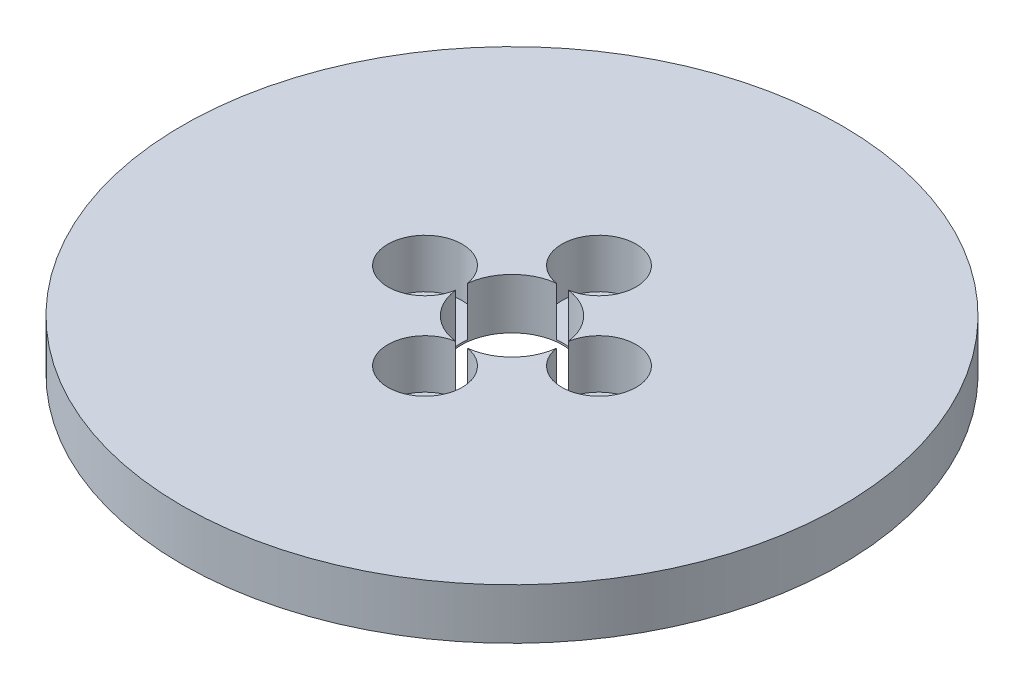
SolidWorks part; units mm, degrees
ref_plane "Front Plane" through (0, 0, 0) normal (0, 0, 1) x (1, 0, 0)
ref_plane "Top Plane" through (0, 0, 0) normal (0, 1, 0) x (1, 0, 0)
ref_plane "Right Plane" through (0, 0, 0) normal (1, 0, 0) x (0, 0, -1)
sketch "Sketch1" plane through (0, 0, 0) normal (0, 1, 0) x (1, 0, 0)
  circle A0 centre (0, 0) radius 65
  dimension "FLANGE_OD" = 130
extrude "Boss-Extrude1" add sketch "Sketch1" along normal blind 10
sketch "Sketch2" plane through (0, 0, 0) normal (0, 1, 0) x (1, 0, 0)
  circle A0 centre (0, 0) radius 10
  dimension "BORE_D" = 20
extrude "Cut-Extrude1" cut sketch "Sketch2" along normal through all
sketch "Sketch3" plane through (0, 10, 0) normal (0, 1, 0) x (1, 0, 0)
  circle A0 centre (0, 0) radius 17.1571 construction
  circle A1 centre (-17.1571, 0) radius 7.3189
  dimension "BOLT_D" = 14.6379
  dimension "BOLT_PCD" = 34.3141
extrude "Cut-Extrude2" cut sketch "Sketch3" against normal blind 9.6516
pattern_circular "CirPattern1" count 4 over 360 about axis through (0, 0, 0) along (0, 1, 0) of "Cut-Extrude2"
